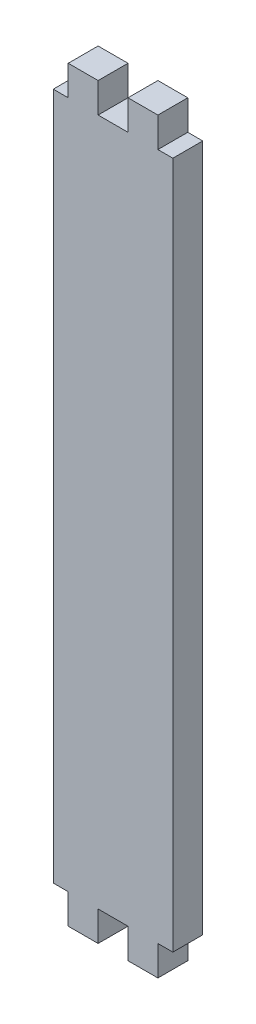
SolidWorks part; units mm, degrees
ref_plane "Front Plane" through (0, 0, 0) normal (0, 0, 1) x (1, 0, 0)
ref_plane "Top Plane" through (0, 0, 0) normal (0, 1, 0) x (1, 0, 0)
ref_plane "Right Plane" through (0, 0, 0) normal (1, 0, 0) x (0, 0, -1)
sketch "Sketch1" plane through (0, 0, 0) normal (0, 0, 1) x (1, 0, 0)
  line L0 (-7.5, 57.5) -> (-7.5, 62.5)
  line L1 (-10, -57.5) -> (-7.5, -57.5)
  line L2 (-10, -57.5) -> (-10, 57.5)
  line L3 (-10, 57.5) -> (-7.5, 57.5)
  line L4 (10, -57.5) -> (10, 57.5)
  line L5 (-10, -57.5) -> (10, 57.5) construction
  line L6 (-10, 57.5) -> (10, -57.5) construction
  line L7 (-7.5, 62.5) -> (-2.5, 62.5)
  line L8 (-2.5, 62.5) -> (-2.5, 57.5)
  line L9 (2.5, 57.5) -> (2.5, 62.5)
  line L10 (2.5, 62.5) -> (7.5, 62.5)
  line L11 (7.5, 62.5) -> (7.5, 57.5)
  line L12 (-2.5, 57.5) -> (2.5, 57.5)
  line L13 (7.5, 57.5) -> (10, 57.5)
  line L14 (-2.5, -57.5) -> (2.5, -57.5)
  line L16 (-7.5, -57.5) -> (-7.5, -62.5)
  line L17 (-7.5, -62.5) -> (-2.5, -62.5)
  line L18 (-2.5, -57.5) -> (-2.5, -62.5)
  line L20 (2.5, -57.5) -> (2.5, -62.5)
  line L21 (2.5, -62.5) -> (7.5, -62.5)
  line L22 (7.5, -57.5) -> (7.5, -62.5)
  line L23 (7.5, -57.5) -> (10, -57.5)
  point P0 (0, 0)
  point P24 (22.918, 10.8491)
  dimension "D1" = 5
  dimension "D2" = 5
  dimension "D3" = 20
  dimension "D4" = 5
  dimension "D5" = 115
extrude "Boss-Extrude1" add sketch "Sketch1" along normal blind 5
